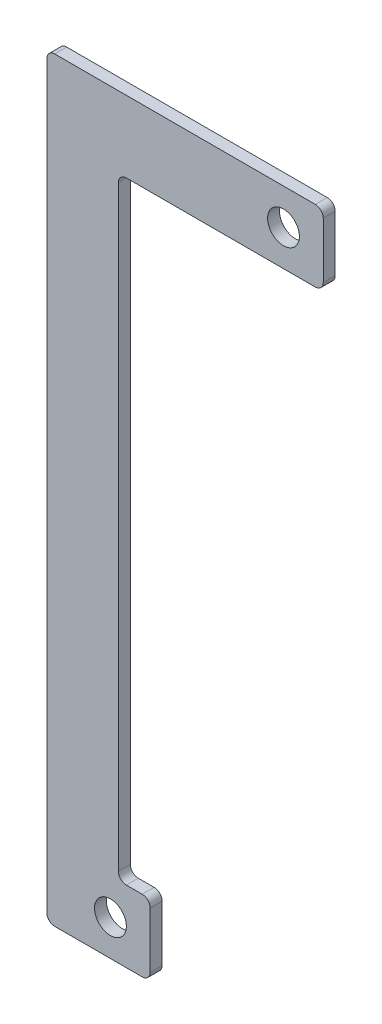
SolidWorks part; units mm, degrees
ref_plane "Front Plane" through (0, 0, 0) normal (0, 0, 1) x (1, 0, 0)
ref_plane "Top Plane" through (0, 0, 0) normal (0, 1, 0) x (1, 0, 0)
ref_plane "Right Plane" through (0, 0, 0) normal (1, 0, 0) x (0, 0, -1)
sketch "Sketch1" plane through (0, 0, 0) normal (0, 0, 1) x (1, 0, 0)
  line L0 (13, 8) -> (13, 1)
  line L1 (12, 0) -> (1, 0)
  line L2 (0, 1) -> (0, 94)
  line L3 (1, 95) -> (33.76, 95)
  line L4 (34.76, 94) -> (34.76, 87)
  line L5 (33.76, 86) -> (10, 86)
  line L6 (9, 85) -> (9, 10)
  line L7 (10, 9) -> (12, 9)
  line L8 (55, 0) -> (-55, 0) construction
  line L9 (29.76, 90.5) -> (29.76, 86) construction
  line L10 (29.76, 90.5) -> (29.76, 95) construction
  line L11 (10, 9) -> (0, 9) construction
  line L12 (8, 9) -> (8, 4.5) construction
  line L13 (8, 4.5) -> (8, 0) construction
  arc A0 (0, 94) -> (1, 95) centre (1, 94) cw
  arc A1 (13, 1) -> (12, 0) centre (12, 1) cw
  arc A2 (1, 0) -> (0, 1) centre (1, 1) cw
  arc A3 (9, 10) -> (10, 9) centre (10, 10) ccw
  arc A4 (13, 8) -> (12, 9) centre (12, 8) ccw
  arc A5 (10, 86) -> (9, 85) centre (10, 85) ccw
  arc A6 (34.76, 87) -> (33.76, 86) centre (33.76, 87) cw
  arc A7 (33.76, 95) -> (34.76, 94) centre (33.76, 94) cw
  circle A8 centre (29.76, 90.5) radius 2
  circle A9 centre (8, 4.5) radius 2
  dimension "D1" = 1
  dimension "D2" = 1
  dimension "D10" = 4
  dimension "D13" = 4
  dimension "D3" = 9
  dimension "D4" = 4
  dimension "D5" = 9
  dimension "D6" = 9
  dimension "D7" = 95
  dimension "D8" = 34.76
  dimension "D9" = 0
  dimension "D11" = 5
  dimension "D12" = 5
extrude "Boss-Extrude1" add sketch "Sketch1" along normal blind 1.5
